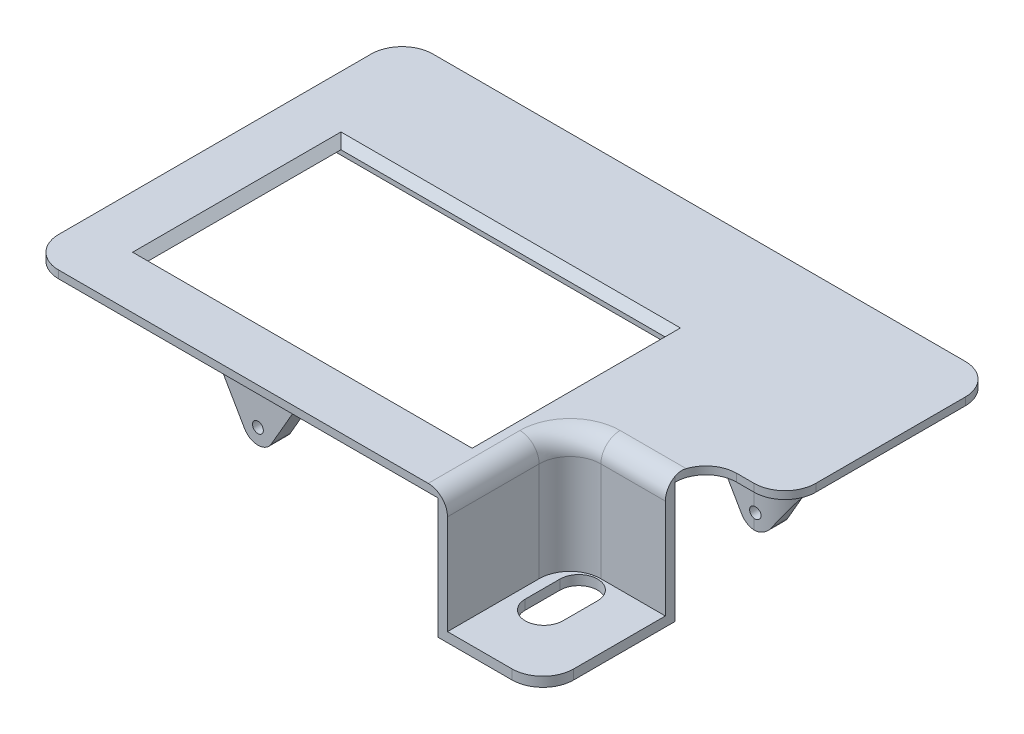
SolidWorks part; units mm, degrees
ref_plane "Front Plane" through (0, 0, 0) normal (0, 0, 1) x (1, 0, 0)
ref_plane "Top Plane" through (0, 0, 0) normal (0, 1, 0) x (1, 0, 0)
ref_plane "Right Plane" through (0, 0, 0) normal (1, 0, 0) x (0, 0, -1)
sketch "Sketch1" plane through (0, 0, 0) normal (0, 1, 0) x (1, 0, 0)
  line L0 (-77, 40.5) -> (-77, -40.5)
  line L1 (-69, -48.5) -> (29.28, -48.5)
  line L2 (29.28, -48.5) -> (29.28, -46)
  line L3 (29.28, -46) -> (-66.5, -46) construction
  line L4 (-74.5, -38) -> (-74.5, 38) construction
  line L5 (-66.5, 46) -> (66.5, 46) construction
  line L6 (74.5, 38) -> (74.5, 4.25) construction
  line L7 (66.5, -3.75) -> (62, -3.75) construction
  line L8 (54, -11.75) -> (54, -14.25) construction
  line L9 (54, -14.25) -> (56.5, -14.25)
  line L10 (64.5, -6.25) -> (69, -6.25)
  line L11 (77, 1.75) -> (77, 40.5)
  line L12 (69, 48.5) -> (-69, 48.5)
  line L13 (29.28, -46) -> (29.28, -14.25)
  line L14 (29.28, -14.25) -> (54, -14.25)
  arc A0 (-77, -40.5) -> (-69, -48.5) centre (-69, -40.5) ccw
  arc A1 (-74.5, -38) -> (-66.5, -46) centre (-66.5, -38) ccw construction
  arc A2 (-66.5, 46) -> (-74.5, 38) centre (-66.5, 38) ccw construction
  arc A3 (74.5, 38) -> (66.5, 46) centre (66.5, 38) ccw construction
  arc A4 (66.5, -3.75) -> (74.5, 4.25) centre (66.5, 4.25) ccw construction
  arc A5 (62, -3.75) -> (54, -11.75) centre (62, -11.75) ccw construction
  arc A6 (64.5, -6.25) -> (56.5, -14.25) centre (64.5, -14.25) ccw
  arc A7 (69, -6.25) -> (77, 1.75) centre (69, 1.75) ccw
  arc A8 (77, 40.5) -> (69, 48.5) centre (69, 40.5) ccw
  arc A9 (-69, 48.5) -> (-77, 40.5) centre (-69, 40.5) ccw
extrude "Boss-Extrude1" add sketch "Sketch1" along normal blind 2
sketch "Sketch2" plane through (0, 0, 0) normal (0, -1, 0) x (1, 0, 0)
  line L0 (54, 11.75) -> (54, 14.25) construction
  line L1 (66.5, 3.75) -> (62, 3.75) construction
  line L2 (74.5, -38) -> (74.5, -4.25) construction
  line L3 (-66.5, -46) -> (66.5, -46) construction
  line L4 (-74.5, 38) -> (-74.5, -38) construction
  line L5 (29.28, 46) -> (-66.5, 46) construction
  line L6 (54, 11.75) -> (54, 14.25)
  line L21 (66.5, 3.75) -> (62, 3.75)
  line L22 (74.5, -38) -> (74.5, -4.25)
  line L23 (-66.5, -46) -> (66.5, -46)
  line L24 (-74.5, 38) -> (-74.5, -38)
  line L25 (29.28, 46) -> (-66.5, 46)
  line L26 (29.28, 44) -> (-66.5, 44)
  line L27 (-72.5, 38) -> (-72.5, -38)
  line L28 (-66.5, -44) -> (66.5, -44)
  line L29 (72.5, -38) -> (72.5, -4.25)
  line L30 (66.5, 1.75) -> (62, 1.75)
  line L31 (52, 11.75) -> (52, 14.25)
  line L32 (29.28, 46) -> (29.28, 44)
  line L33 (54, 14.25) -> (52, 14.25)
  arc A0 (-74.5, -38) -> (-66.5, -46) centre (-66.5, -38) ccw construction
  arc A1 (54, 11.75) -> (62, 3.75) centre (62, 11.75) ccw construction
  arc A2 (74.5, -4.25) -> (66.5, 3.75) centre (66.5, -4.25) ccw construction
  arc A3 (66.5, -46) -> (74.5, -38) centre (66.5, -38) ccw construction
  arc A4 (-66.5, 46) -> (-74.5, 38) centre (-66.5, 38) ccw construction
  arc A15 (-74.5, -38) -> (-66.5, -46) centre (-66.5, -38) ccw
  arc A16 (54, 11.75) -> (62, 3.75) centre (62, 11.75) ccw
  arc A17 (74.5, -4.25) -> (66.5, 3.75) centre (66.5, -4.25) ccw
  arc A18 (66.5, -46) -> (74.5, -38) centre (66.5, -38) ccw
  arc A19 (-66.5, 46) -> (-74.5, 38) centre (-66.5, 38) ccw
  arc A20 (-66.5, 44) -> (-72.5, 38) centre (-66.5, 38) ccw
  arc A21 (-72.5, -38) -> (-66.5, -44) centre (-66.5, -38) ccw
  arc A22 (66.5, -44) -> (72.5, -38) centre (66.5, -38) ccw
  arc A23 (72.5, -4.25) -> (66.5, 1.75) centre (66.5, -4.25) ccw
  arc A24 (52, 11.75) -> (62, 1.75) centre (62, 11.75) ccw
  dimension "D1" = 2
extrude "Boss-Extrude2" add sketch "Sketch2" along normal blind 2
sketch "Sketch3" plane through (0, 0, 14.25) normal (0, 0, 1) x (1, 0, 0)
  line L0 (29.28, 2) -> (29.28, 0) construction
  line L5 (56.5, 2) -> (29.28, 2)
  line L6 (56.5, 2) -> (56.5, -31.28)
  line L7 (56.5, -31.28) -> (29.28, -31.28)
  line L8 (29.28, 2) -> (29.28, -31.28)
  dimension "D1" = 33.28
extrude "Boss-Extrude3" add sketch "Sketch3" along normal blind 2.5
sketch "Sketch4" plane through (29.28, 0, 0) normal (1, 0, 0) x (0, 0, -1)
  line L1 (-48.5, 2) -> (-16.75, 2)
  line L2 (-48.5, 2) -> (-48.5, -31.28)
  line L3 (-48.5, -31.28) -> (-16.75, -31.28)
  line L4 (-16.75, 2) -> (-16.75, -31.28)
extrude "Boss-Extrude4" add sketch "Sketch4" along normal blind 2.5
sketch "Sketch5" plane through (0, -31.28, 0) normal (0, -1, 0) x (1, 0, 0)
  line L0 (-69, 48.5) -> (29.28, 48.5) construction
  line L1 (29.28, 14.25) -> (56.5, 14.25)
  line L2 (29.28, 14.25) -> (29.28, 48.5)
  line L3 (29.28, 48.5) -> (56.5, 48.5)
  line L4 (56.5, 14.25) -> (56.5, 48.5)
  line L5 (56.5, 16.75) -> (56.5, 14.25) construction
extrude "Boss-Extrude5" add sketch "Sketch5" against normal blind 2.5
fillet "Fillet1" radius 8 1 edges at (56.5, -30.03, 48.5)
sketch "Sketch6" plane through (0, -28.78, 0) normal (0, 1, 0) x (1, 0, 0)
  line L0 (39.43, -22.12) -> (39.43, -31.12) construction
  line L1 (44.31, -22.12) -> (44.31, -31.12)
  line L2 (34.55, -22.12) -> (34.55, -31.12)
  line L3 (56.5, -16.75) -> (56.5, -40.5) construction
  line L4 (48.5, -48.5) -> (31.78, -48.5) construction
  arc A0 (44.31, -22.12) -> (34.55, -22.12) centre (39.43, -22.12) ccw
  arc A1 (34.55, -31.12) -> (44.31, -31.12) centre (39.43, -31.12) ccw
  point P2 (39.43, -26.62)
  dimension "D2" = 4.88
  dimension "D1" = 9
  dimension "D3" = 21.95
  dimension "D4" = 26.38
extrude "Cut-Extrude1" cut sketch "Sketch6" against normal up to next
fillet "Fillet3" radius 8 2 edges at (29.28, -15.64, 14.25) (31.78, -13.39, 16.75)
fillet "Fillet6" radius 5 3 edges at (31.78, 2, 36.625) (34.1231, 2, 19.0931) (48.14, 2, 16.75)
sketch "Sketch7" plane through (0, 0, 0) normal (0, -1, 0) x (1, 0, 0)
  line L0 (-77, -40.5) -> (-77, 40.5) construction
  line L1 (27.38, -21.88) -> (-69.62, -21.88)
  line L2 (27.38, -21.88) -> (27.38, 36.92)
  line L3 (27.38, 36.92) -> (-69.62, 36.92)
  line L4 (-69.62, -21.88) -> (-69.62, 36.92)
  line L5 (27.38, -21.88) -> (-69.62, 36.92) construction
  line L6 (27.38, 36.92) -> (-69.62, -21.88) construction
  line L7 (-69, 48.5) -> (29.28, 48.5) construction
  line L8 (-71.62, -23.88) -> (-71.62, 38.92)
  line L9 (29.38, 38.92) -> (-71.62, 38.92)
  line L10 (29.38, -23.88) -> (29.38, 38.92)
  line L11 (29.38, -23.88) -> (-71.62, -23.88)
  point P0 (-21.12, 7.52)
  dimension "D1" = 97
  dimension "D2" = 58.8
  dimension "D3" = 7.38
  dimension "D4" = 11.58
  dimension "D5" = 2
extrude "Boss-Extrude6" add sketch "Sketch7" along normal blind 6
sketch "Sketch8" plane through (0, 2, 0) normal (0, 1, 0) x (1, 0, 0)
  line L0 (-69, -48.5) -> (29.28, -48.5) construction
  line L1 (-61.42, 17.08) -> (22.58, 17.08)
  line L2 (-61.42, 17.08) -> (-61.42, -32.92)
  line L3 (-61.42, -32.92) -> (22.58, -32.92)
  line L4 (22.58, 17.08) -> (22.58, -32.92)
  line L5 (-61.42, 17.08) -> (22.58, -32.92) construction
  line L6 (-61.42, -32.92) -> (22.58, 17.08) construction
  line L7 (-77, 40.5) -> (-77, -40.5) construction
  point P0 (-19.42, -7.92)
  dimension "D1" = 50
  dimension "D2" = 84
  dimension "D3" = 15.58
  dimension "D4" = 15.58
extrude "Cut-Extrude2" cut sketch "Sketch8" against normal up to next
chamfer "Chamfer1" distance 2 angle 45 4 edges at (-19.42, 2, 32.92) (-61.42, 2, 7.92) (-19.42, 2, -17.08) (22.58, 2, 7.92)
sketch "Sketch9" plane through (0, 0, 48.5) normal (0, 0, 1) x (1, 0, 0)
  line L0 (-77, 2) -> (-77, 0) construction
  line L1 (-23.3241, -12) -> (-30.2523, 0)
  line L2 (-30.2523, 0) -> (-9.4677, 0)
  line L3 (69, 0) -> (-69, 0) construction
  line L4 (-9.4677, 0) -> (-16.3959, -12)
  circle A0 centre (-19.86, -10) radius 1.4
  arc A1 (-23.3241, -12) -> (-16.3959, -12) centre (-19.86, -10) ccw
  dimension "D1" = 2.8
  dimension "D2" = 8
  dimension "D3" = 57.14
  dimension "D4" = 10
  dimension "D5" = 60
extrude "Boss-Extrude7" add sketch "Sketch9" against normal blind 5 from surface starting at face at (-18.61, -1, 46)
sketch "Sketch10" plane through (0, 0, 0) normal (0, 0, 1) x (1, 0, 0)
  line L1 (77, 0) -> (69, 0) construction
  line L2 (77, 2) -> (77, 0) construction
  line L3 (70.2141, -9) -> (75.4103, 0)
  line L4 (75.4103, 0) -> (58.0897, 0)
  line L5 (69, 0) -> (-69, 0) construction
  line L6 (58.0897, 0) -> (63.2859, -9)
  arc A0 (63.2859, -9) -> (70.2141, -9) centre (66.75, -7) ccw
  circle A1 centre (66.75, -7) radius 1.4
  dimension "D1" = 2.8
  dimension "D2" = 8
  dimension "D3" = 10.25
  dimension "D4" = 7
  dimension "D5" = 60
extrude "Boss-Extrude8" add sketch "Sketch10" against normal blind 5 from surface starting at face at (64.25, -1, 3.75)
sketch "Sketch11" plane through (0, 0, -46) normal (0, 0, -1) x (-1, 0, 0)
  line L0 (-69, 0) -> (69, 0) construction
  line L1 (77, 2) -> (77, 0) construction
  line L2 (-77, 2) -> (-77, 0) construction
  line L3 (-65.4641, -9) -> (-70.6603, 0)
  line L5 (-70.6603, 0) -> (-53.3397, 0)
  line L6 (-53.3397, 0) -> (-58.5359, -9)
  line L7 (-69, 0) -> (-77, 0) construction
  line L8 (58.5359, -9) -> (53.3397, 0)
  line L12 (70.6603, 0) -> (65.4641, -9)
  line L13 (77, 0) -> (69, 0) construction
  line L14 (53.3397, 0) -> (70.6603, 0)
  circle A0 centre (-62, -7) radius 1.4
  circle A1 centre (62, -7) radius 1.4
  arc A2 (-65.4641, -9) -> (-58.5359, -9) centre (-62, -7) ccw
  arc A3 (58.5359, -9) -> (65.4641, -9) centre (62, -7) ccw
  dimension "D4" = 2.8
  dimension "D5" = 8
  dimension "D1" = 7
  dimension "D2" = 15
  dimension "D3" = 15
  dimension "D6" = 60
  dimension "D7" = 60
extrude "Boss-Extrude9" add sketch "Sketch11" against normal blind 5
sketch "Sketch12" plane through (0, 0, 0) normal (0, -1, 0) x (1, 0, 0)
  line L0 (-66.5, -46) -> (66.5, -46) construction
  line L1 (66.5, 3.75) -> (62, 3.75) construction
  line L2 (-66.5, -46) -> (66.5, -46)
  line L3 (66.5, 3.75) -> (62, 3.75)
  line L4 (54, 11.75) -> (84.2957, 11.75)
  line L5 (84.2957, 11.75) -> (84.2957, -4.25)
  line L6 (84.2957, -4.25) -> (74.5, -4.25)
  line L7 (74.5, -38) -> (84.2957, -38)
  line L8 (84.2957, -38) -> (84.2957, -62.9296)
  line L9 (84.2957, -62.9296) -> (-82.1257, -61.468)
  line L10 (-82.1257, -61.468) -> (-82.1257, -38)
  line L11 (-82.1257, -38) -> (-74.5, -38)
  arc A0 (66.5, -46) -> (74.5, -38) centre (66.5, -38) ccw construction
  arc A1 (-74.5, -38) -> (-66.5, -46) centre (-66.5, -38) ccw construction
  arc A2 (54, 11.75) -> (62, 3.75) centre (62, 11.75) ccw construction
  arc A3 (74.5, -4.25) -> (66.5, 3.75) centre (66.5, -4.25) ccw construction
  arc A4 (66.5, -46) -> (74.5, -38) centre (66.5, -38) ccw
  arc A5 (-74.5, -38) -> (-66.5, -46) centre (-66.5, -38) ccw
  arc A6 (54, 11.75) -> (62, 3.75) centre (62, 11.75) ccw
  arc A7 (74.5, -4.25) -> (66.5, 3.75) centre (66.5, -4.25) ccw
extrude "Cut-Extrude3" cut sketch "Sketch12" along normal through all
sketch "Sketch13" plane through (0, -6, 0) normal (0, -1, 0) x (1, 0, 0)
  line L0 (-71.62, 38.92) -> (-71.62, -23.88) construction
  line L1 (-71.62, 22.22) -> (-69.62, 22.22)
  line L2 (-71.62, 22.22) -> (-71.62, 17.22)
  line L3 (-71.62, 17.22) -> (-69.62, 17.22)
  line L4 (-69.62, 22.22) -> (-69.62, 17.22)
  line L5 (-69.62, 36.92) -> (-69.62, -21.88) construction
  line L7 (-71.62, 19.72) -> (-69.62, 19.72) construction
  line L8 (29.28, 38.92) -> (-71.62, 38.92) construction
  line L9 (-71.62, 38.92) -> (-71.62, -23.88) construction
  line L10 (-71.62, -2.18) -> (-69.62, -2.18)
  line L11 (-71.62, -2.18) -> (-71.62, -7.18)
  line L12 (-71.62, -7.18) -> (-69.62, -7.18)
  line L13 (-69.62, -2.18) -> (-69.62, -7.18)
  line L14 (-71.62, -4.68) -> (-69.62, -4.68) construction
  line L15 (-71.62, -23.88) -> (29.38, -23.88) construction
  dimension "D1" = 5
  dimension "D2" = 19.2
  dimension "D3" = 5
  dimension "D4" = 19.2
extrude "Cut-Extrude4" cut sketch "Sketch13" against normal up to surface (6 mm away) up to face at (-21.12, 0, 7.52)
